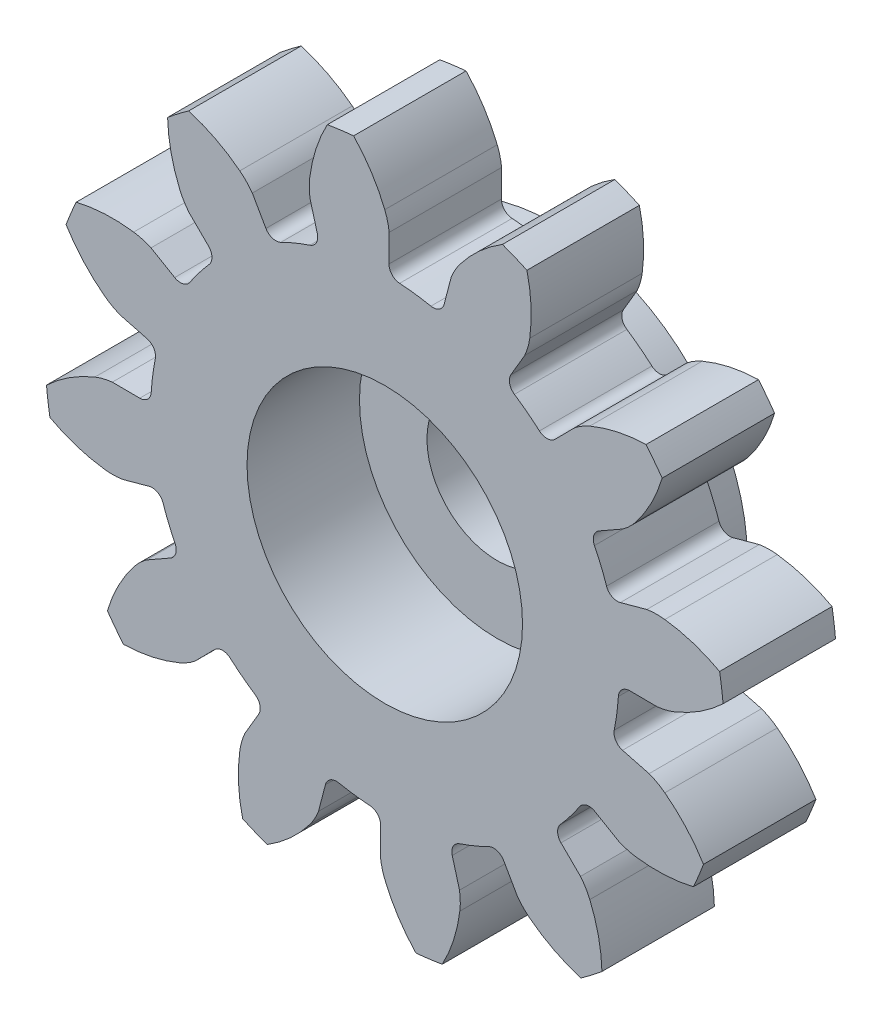
SolidWorks part; units mm, degrees
ref_plane "Front Plane" through (0, 0, 0) normal (0, 0, 1) x (1, 0, 0)
ref_plane "Top Plane" through (0, 0, 0) normal (0, 1, 0) x (1, 0, 0)
ref_plane "Right Plane" through (0, 0, 0) normal (1, 0, 0) x (0, 0, -1)
sketch "Sketch1" plane through (0, 0, 0) normal (0, 0, 1) x (1, 0, 0)
  line L48 (-1.3289, 4.6605) -> (-1.1999, 4.1898)
  line L49 (-2.1142, 3.8111) -> (-2.3558, 4.2352)
  line L50 (-3.4812, 3.3716) -> (-3.134, 3.0285)
  line L51 (-3.7365, 2.2434) -> (-4.1577, 2.4899)
  line L52 (-4.7006, 1.1794) -> (-4.2284, 1.0558)
  line L53 (-4.3576, 0.0746) -> (-4.8457, 0.0774)
  line L54 (-4.6605, -1.3289) -> (-4.1898, -1.1999)
  line L55 (-3.8111, -2.1142) -> (-4.2352, -2.3558)
  line L56 (-3.3716, -3.4812) -> (-3.0285, -3.134)
  line L57 (-2.2434, -3.7365) -> (-2.4899, -4.1577)
  line L58 (-1.1794, -4.7006) -> (-1.0558, -4.2284)
  line L59 (-0.0746, -4.3576) -> (-0.0774, -4.8457)
  line L60 (1.3289, -4.6605) -> (1.1999, -4.1898)
  line L61 (2.1142, -3.8111) -> (2.3558, -4.2352)
  line L62 (3.4812, -3.3716) -> (3.134, -3.0285)
  line L63 (3.7365, -2.2434) -> (4.1577, -2.4899)
  line L64 (4.7006, -1.1794) -> (4.2284, -1.0558)
  line L65 (4.3576, -0.0746) -> (4.8457, -0.0774)
  line L66 (4.6605, 1.3289) -> (4.1898, 1.1999)
  line L67 (3.8111, 2.1142) -> (4.2352, 2.3558)
  line L68 (3.3716, 3.4812) -> (3.0285, 3.134)
  line L69 (2.2434, 3.7365) -> (2.4899, 4.1577)
  line L70 (1.1794, 4.7006) -> (1.0558, 4.2284)
  line L71 (0.0746, 4.3576) -> (0.0774, 4.8457)
  circle A0 centre (0, 0) radius 2.45
  arc A192 (0.0002, 5.1569) -> (-0.5543, 6.0169) centre (-2.5558, 4.1176) ccw
  arc A193 (-0.5543, 6.0169) -> (-1.0218, 5.9553) centre (0, 0) ccw
  arc A194 (-1.0218, 5.9553) -> (-1.3349, 4.9811) centre (1.403, 4.6388) ccw
  arc A195 (-1.3349, 4.9811) -> (-1.3289, 4.6605) centre (-0.2176, 4.8414) ccw
  arc A196 (-1.3304, 3.9445) -> (-1.1999, 4.1898) centre (-1.3951, 4.1363) ccw
  arc A197 (-1.3304, 3.9445) -> (-1.8484, 3.7299) centre (0, 0) ccw
  arc A198 (-2.1142, 3.8111) -> (-1.8484, 3.7299) centre (-1.9383, 3.9113) ccw
  arc A199 (-2.3558, 4.2352) -> (-2.5783, 4.4661) centre (-3.2695, 3.5772) ccw
  arc A200 (-2.5783, 4.4661) -> (-3.4885, 4.9336) centre (-4.2721, 2.288) ccw
  arc A201 (-3.4885, 4.9336) -> (-3.8626, 4.6465) centre (0, 0) ccw
  arc A202 (-3.8626, 4.6465) -> (-3.6466, 3.6463) centre (-1.1044, 4.7188) ccw
  arc A203 (-3.6466, 3.6463) -> (-3.4812, 3.3716) centre (-2.6091, 4.084) ccw
  arc A204 (-3.1244, 2.7508) -> (-3.134, 3.0285) centre (-3.2763, 2.8846) ccw
  arc A205 (-3.1244, 2.7508) -> (-3.4657, 2.306) centre (0, 0) ccw
  arc A206 (-3.7365, 2.2434) -> (-3.4657, 2.306) centre (-3.6343, 2.4181) ccw
  arc A207 (-4.1577, 2.4899) -> (-4.4659, 2.5786) centre (-4.6201, 1.4632) ccw
  arc A208 (-4.4659, 2.5786) -> (-5.4879, 2.5284) centre (-4.8438, -0.1546) ccw
  arc A209 (-5.4879, 2.5284) -> (-5.6684, 2.0927) centre (0, 0) ccw
  arc A210 (-5.6684, 2.0927) -> (-4.9812, 1.3345) centre (-3.3158, 3.5344) ccw
  arc A211 (-4.9812, 1.3345) -> (-4.7006, 1.1794) centre (-4.3015, 2.2323) ccw
  arc A212 (-4.0812, 0.8201) -> (-4.2284, 1.0558) centre (-4.2797, 0.86) ccw
  arc A213 (-4.0812, 0.8201) -> (-4.1544, 0.2642) centre (0, 0) ccw
  arc A214 (-4.3576, 0.0746) -> (-4.1544, 0.2642) centre (-4.3564, 0.277) ccw
  arc A215 (-4.8457, 0.0774) -> (-5.1569, 0.0002) centre (-4.7327, -1.0429) ccw
  arc A216 (-5.1569, 0.0002) -> (-6.0169, -0.5543) centre (-4.1176, -2.5558) ccw
  arc A217 (-6.0169, -0.5543) -> (-5.9553, -1.0218) centre (0, 0) ccw
  arc A218 (-5.9553, -1.0218) -> (-4.9811, -1.3349) centre (-4.6388, 1.403) ccw
  arc A219 (-4.9811, -1.3349) -> (-4.6605, -1.3289) centre (-4.8414, -0.2176) ccw
  arc A220 (-3.9445, -1.3304) -> (-4.1898, -1.1999) centre (-4.1363, -1.3951) ccw
  arc A221 (-3.9445, -1.3304) -> (-3.7299, -1.8484) centre (0, 0) ccw
  arc A222 (-3.8111, -2.1142) -> (-3.7299, -1.8484) centre (-3.9113, -1.9383) ccw
  arc A223 (-4.2352, -2.3558) -> (-4.4661, -2.5783) centre (-3.5772, -3.2695) ccw
  arc A224 (-4.4661, -2.5783) -> (-4.9336, -3.4885) centre (-2.288, -4.2721) ccw
  arc A225 (-4.9336, -3.4885) -> (-4.6465, -3.8626) centre (0, 0) ccw
  arc A226 (-4.6465, -3.8626) -> (-3.6463, -3.6466) centre (-4.7188, -1.1044) ccw
  arc A227 (-3.6463, -3.6466) -> (-3.3716, -3.4812) centre (-4.084, -2.6091) ccw
  arc A228 (-2.7508, -3.1244) -> (-3.0285, -3.134) centre (-2.8846, -3.2763) ccw
  arc A229 (-2.7508, -3.1244) -> (-2.306, -3.4657) centre (0, 0) ccw
  arc A230 (-2.2434, -3.7365) -> (-2.306, -3.4657) centre (-2.4181, -3.6343) ccw
  arc A231 (-2.4899, -4.1577) -> (-2.5786, -4.4659) centre (-1.4632, -4.6201) ccw
  arc A232 (-2.5786, -4.4659) -> (-2.5284, -5.4879) centre (0.1546, -4.8438) ccw
  arc A233 (-2.5284, -5.4879) -> (-2.0927, -5.6684) centre (0, 0) ccw
  arc A234 (-2.0927, -5.6684) -> (-1.3345, -4.9812) centre (-3.5344, -3.3158) ccw
  arc A235 (-1.3345, -4.9812) -> (-1.1794, -4.7006) centre (-2.2323, -4.3015) ccw
  arc A236 (-0.8201, -4.0812) -> (-1.0558, -4.2284) centre (-0.86, -4.2797) ccw
  arc A237 (-0.8201, -4.0812) -> (-0.2642, -4.1544) centre (0, 0) ccw
  arc A238 (-0.0746, -4.3576) -> (-0.2642, -4.1544) centre (-0.277, -4.3564) ccw
  arc A239 (-0.0774, -4.8457) -> (-0.0002, -5.1569) centre (1.0429, -4.7327) ccw
  arc A240 (-0.0002, -5.1569) -> (0.5543, -6.0169) centre (2.5558, -4.1176) ccw
  arc A241 (0.5543, -6.0169) -> (1.0218, -5.9553) centre (0, 0) ccw
  arc A242 (1.0218, -5.9553) -> (1.3349, -4.9811) centre (-1.403, -4.6388) ccw
  arc A243 (1.3349, -4.9811) -> (1.3289, -4.6605) centre (0.2176, -4.8414) ccw
  arc A244 (1.3304, -3.9445) -> (1.1999, -4.1898) centre (1.3951, -4.1363) ccw
  arc A245 (1.3304, -3.9445) -> (1.8484, -3.7299) centre (0, 0) ccw
  arc A246 (2.1142, -3.8111) -> (1.8484, -3.7299) centre (1.9383, -3.9113) ccw
  arc A247 (2.3558, -4.2352) -> (2.5783, -4.4661) centre (3.2695, -3.5772) ccw
  arc A248 (2.5783, -4.4661) -> (3.4885, -4.9336) centre (4.2721, -2.288) ccw
  arc A249 (3.4885, -4.9336) -> (3.8626, -4.6465) centre (0, 0) ccw
  arc A250 (3.8626, -4.6465) -> (3.6466, -3.6463) centre (1.1044, -4.7188) ccw
  arc A251 (3.6466, -3.6463) -> (3.4812, -3.3716) centre (2.6091, -4.084) ccw
  arc A252 (3.1244, -2.7508) -> (3.134, -3.0285) centre (3.2763, -2.8846) ccw
  arc A253 (3.1244, -2.7508) -> (3.4657, -2.306) centre (0, 0) ccw
  arc A254 (3.7365, -2.2434) -> (3.4657, -2.306) centre (3.6343, -2.4181) ccw
  arc A255 (4.1577, -2.4899) -> (4.4659, -2.5786) centre (4.6201, -1.4632) ccw
  arc A256 (4.4659, -2.5786) -> (5.4879, -2.5284) centre (4.8438, 0.1546) ccw
  arc A257 (5.4879, -2.5284) -> (5.6684, -2.0927) centre (0, 0) ccw
  arc A258 (5.6684, -2.0927) -> (4.9812, -1.3345) centre (3.3158, -3.5344) ccw
  arc A259 (4.9812, -1.3345) -> (4.7006, -1.1794) centre (4.3015, -2.2323) ccw
  arc A260 (4.0812, -0.8201) -> (4.2284, -1.0558) centre (4.2797, -0.86) ccw
  arc A261 (4.0812, -0.8201) -> (4.1544, -0.2642) centre (0, 0) ccw
  arc A262 (4.3576, -0.0746) -> (4.1544, -0.2642) centre (4.3564, -0.277) ccw
  arc A263 (4.8457, -0.0774) -> (5.1569, -0.0002) centre (4.7327, 1.0429) ccw
  arc A264 (5.1569, -0.0002) -> (6.0169, 0.5543) centre (4.1176, 2.5558) ccw
  arc A265 (6.0169, 0.5543) -> (5.9553, 1.0218) centre (0, 0) ccw
  arc A266 (5.9553, 1.0218) -> (4.9811, 1.3349) centre (4.6388, -1.403) ccw
  arc A267 (4.9811, 1.3349) -> (4.6605, 1.3289) centre (4.8414, 0.2176) ccw
  arc A268 (3.9445, 1.3304) -> (4.1898, 1.1999) centre (4.1363, 1.3951) ccw
  arc A269 (3.9445, 1.3304) -> (3.7299, 1.8484) centre (0, 0) ccw
  arc A270 (3.8111, 2.1142) -> (3.7299, 1.8484) centre (3.9113, 1.9383) ccw
  arc A271 (4.2352, 2.3558) -> (4.4661, 2.5783) centre (3.5772, 3.2695) ccw
  arc A272 (4.4661, 2.5783) -> (4.9336, 3.4885) centre (2.288, 4.2721) ccw
  arc A273 (4.9336, 3.4885) -> (4.6465, 3.8626) centre (0, 0) ccw
  arc A274 (4.6465, 3.8626) -> (3.6463, 3.6466) centre (4.7188, 1.1044) ccw
  arc A275 (3.6463, 3.6466) -> (3.3716, 3.4812) centre (4.084, 2.6091) ccw
  arc A276 (2.7508, 3.1244) -> (3.0285, 3.134) centre (2.8846, 3.2763) ccw
  arc A277 (2.7508, 3.1244) -> (2.306, 3.4657) centre (0, 0) ccw
  arc A278 (2.2434, 3.7365) -> (2.306, 3.4657) centre (2.4181, 3.6343) ccw
  arc A279 (2.4899, 4.1577) -> (2.5786, 4.4659) centre (1.4632, 4.6201) ccw
  arc A280 (2.5786, 4.4659) -> (2.5284, 5.4879) centre (-0.1546, 4.8438) ccw
  arc A281 (2.5284, 5.4879) -> (2.0927, 5.6684) centre (0, 0) ccw
  arc A282 (2.0927, 5.6684) -> (1.3345, 4.9812) centre (3.5344, 3.3158) ccw
  arc A283 (1.3345, 4.9812) -> (1.1794, 4.7006) centre (2.2323, 4.3015) ccw
  arc A284 (0.8201, 4.0812) -> (1.0558, 4.2284) centre (0.86, 4.2797) ccw
  arc A285 (0.8201, 4.0812) -> (0.2642, 4.1544) centre (0, 0) ccw
  arc A286 (0.0746, 4.3576) -> (0.2642, 4.1544) centre (0.277, 4.3564) ccw
  arc A287 (0.0774, 4.8457) -> (0.0002, 5.1569) centre (-1.0429, 4.7327) ccw
  dimension "D1" = 4.9
extrude "Boss-Extrude1" add sketch "Sketch1" along normal blind 2
sketch "Sketch2" plane through (0, 0, 0) normal (0, 0, -1) x (-1, 0, 0)
  circle A0 centre (0, 0) radius 3.45
  circle A1 centre (0, 0) radius 2.45 construction
  circle A2 centre (0, 0) radius 1.25
  dimension "D1" = 1
  dimension "D2" = 2.5
extrude "Boss-Extrude2" add sketch "Sketch2" along normal blind 1
